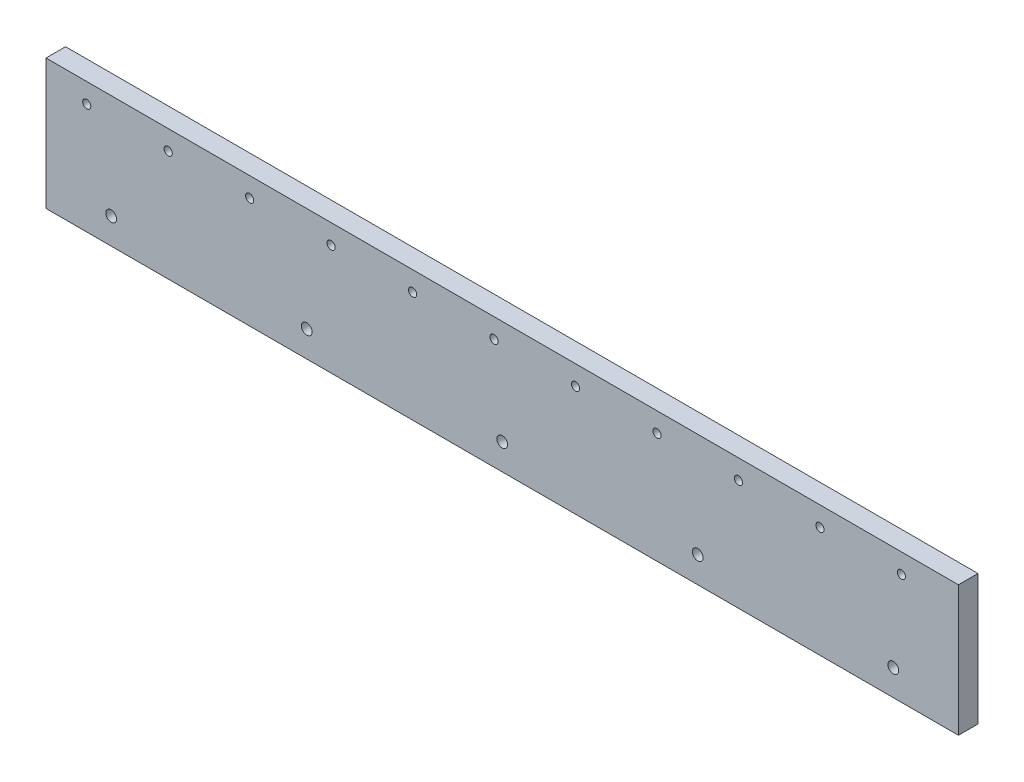
SolidWorks part; units mm, degrees
ref_plane "Front" through (0, 0, 0) normal (0, 0, 1) x (1, 0, 0)
ref_plane "Top" through (0, 0, 0) normal (0, 1, 0) x (1, 0, 0)
ref_plane "Right" through (0, 0, 0) normal (1, 0, 0) x (0, 0, -1)
sketch "Esquisse1" plane through (0, 0, 0) normal (0, 0, 1) x (1, 0, 0)
  line L1 (0, 0) -> (280, 0)
  line L2 (0, 0) -> (0, 40)
  line L3 (0, 40) -> (280, 40)
  line L4 (280, 0) -> (280, 40)
  dimension "D1" = 40
  dimension "D2" = 280
extrude "Boss.-Extru.1" add sketch "Esquisse1" along normal blind 6
sketch "Esquisse2" plane through (0, 0, 6) normal (0, 0, 1) x (1, 0, 0)
  line L0 (0, 34) -> (280, 34) construction
  line L1 (0, 40) -> (0, 0) construction
  line L2 (280, 0) -> (280, 40) construction
  line L3 (280, 40) -> (0, 40) construction
  line L4 (12.5, 34) -> (37.5, 34) construction
  circle A0 centre (12.5, 34) radius 1.25
  circle A1 centre (37.5, 34) radius 1.25
  circle A2 centre (62.5, 34) radius 1.25
  circle A3 centre (87.5, 34) radius 1.25
  circle A4 centre (112.5, 34) radius 1.25
  circle A5 centre (137.5, 34) radius 1.25
  circle A6 centre (162.5, 34) radius 1.25
  circle A7 centre (187.5, 34) radius 1.25
  circle A8 centre (212.5, 34) radius 1.25
  circle A9 centre (237.5, 34) radius 1.25
  circle A10 centre (262.5, 34) radius 1.25
  point P10 (37.5, 34)
  dimension "D1" = 12.5
  dimension "D2" = 2.5
  dimension "D3" = 6
  dimension "D5" = 25
  dimension "D4" = 11
extrude "Enlèv. mat.-Extru.1" cut sketch "Esquisse2" against normal up to vertex (6 mm away) up to point (280, 40, 0)
sketch "Esquisse3" plane through (0, 0, 6) normal (0, 0, 1) x (1, 0, 0)
  line L0 (0, 8) -> (280, 8) construction
  line L1 (0, 40) -> (0, 0) construction
  line L2 (280, 0) -> (280, 40) construction
  line L3 (20, 8) -> (80, 8) construction
  line L4 (140, 8) -> (140, 1.9362) construction
  line L5 (0, 0) -> (280, 0) construction
  circle A0 centre (20, 8) radius 1.65
  circle A1 centre (80, 8) radius 1.65
  circle A2 centre (140, 8) radius 1.65
  circle A3 centre (200, 8) radius 1.65
  circle A4 centre (260, 8) radius 1.65
  point P8 (140.9245, 7.9899)
  dimension "D1" = 3.3
  dimension "D3" = 60
  dimension "D4" = 8
  dimension "D2" = 5
extrude "Enlèv. mat.-Extru.2" cut sketch "Esquisse3" against normal through all and the other way through all
